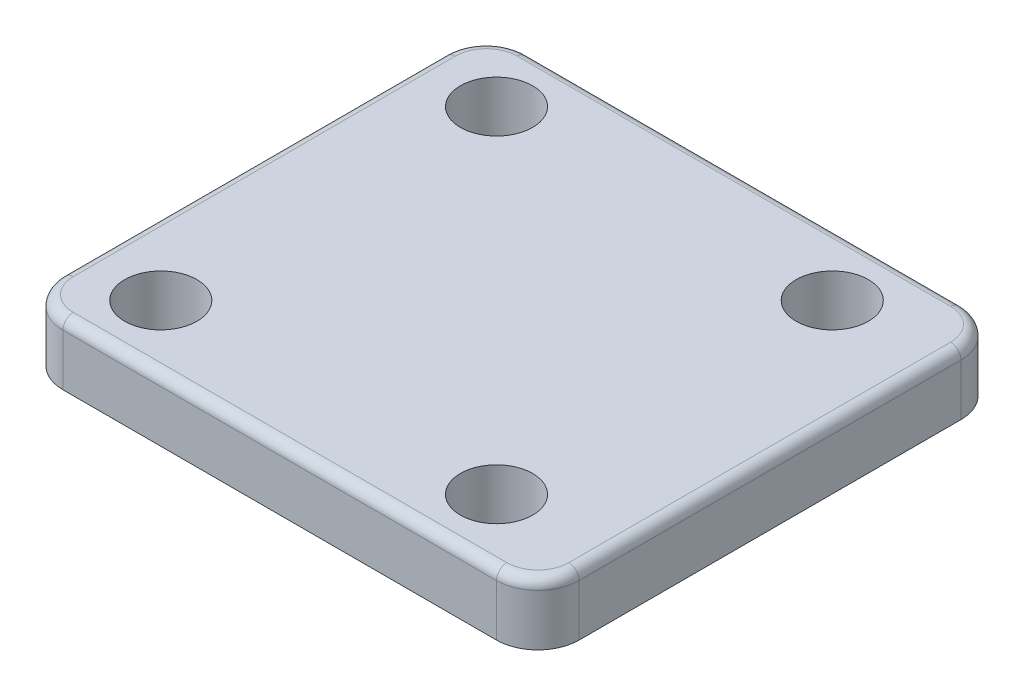
SolidWorks part; units mm, degrees
material "6061 Alloy"
ref_plane "Front Plane" through (0, 0, 0) normal (0, 0, 1) x (1, 0, 0)
ref_plane "Top Plane" through (0, 0, 0) normal (0, 1, 0) x (1, 0, 0)
ref_plane "Right Plane" through (0, 0, 0) normal (1, 0, 0) x (0, 0, -1)
sketch "Sketch1" plane through (0, 0, 0) normal (0, 1, 0) x (1, 0, 0)
  line L1 (-21, -22.5) -> (21, -22.5)
  line L2 (-25, -18.5) -> (-25, 18.5)
  line L3 (-21, 22.5) -> (21, 22.5)
  line L4 (25, -18.5) -> (25, 18.5)
  line L5 (-25, -22.5) -> (25, 22.5) construction
  line L6 (-25, 22.5) -> (25, -22.5) construction
  arc A0 (25, -18.5) -> (21, -22.5) centre (21, -18.5) cw
  arc A1 (-21, -22.5) -> (-25, -18.5) centre (-21, -18.5) cw
  arc A2 (25, 18.5) -> (21, 22.5) centre (21, 18.5) ccw
  arc A3 (-25, 18.5) -> (-21, 22.5) centre (-21, 18.5) cw
  point P0 (0, 0)
  dimension "D3" = 4
  dimension "D1" = 45
  dimension "D2" = 50
extrude "Boss-Extrude1" add sketch "Sketch1" along normal blind 6
fillet "Fillet1" radius 1 8 edges at (0, 6, 22.5) (-23.8284, 6, 21.3284) (-25, 6, 0) (-23.8284, 6, -21.3284) (0, 6, -22.5) (23.8284, 6, -21.3284) (25, 6, 0) (23.8284, 6, 21.3284)
sketch "Sketch2" plane through (0, 0, 0) normal (0, -1, 0) x (1, 0, 0)
  line L1 (-25, -18.5) -> (-25, 18.5) construction
  circle A0 centre (-1.5, 0) radius 16
  dimension "D1" = 32
  dimension "D2" = 23.5
  dimension "D3" = 1.5
extrude "Boss-Extrude2" add sketch "Sketch2" along normal blind 0.5
sketch "Sketch3" plane through (0, -0.5, 0) normal (0, -1, 0) x (-1, 0, 0)
  circle A0 centre (1.5, 0) radius 15
  circle A1 centre (1.5, 0) radius 16 construction
  dimension "D1" = 1
extrude "Boss-Extrude3" add sketch "Sketch3" along normal blind 0.5
fillet "Fillet2" radius 1 1 edges at (-1.5, -0.5, -15) profile chamfer first distance on face at (-1.5, -0.5, -15)
sketch "Sketch5" plane through (0, 0, 0) normal (0, -1, 0) x (-1, 0, 0)
  line L0 (11.5, 10) -> (1.5, 0) construction
  line L1 (-14.7635, -16.2635) -> (-8.5, -10) construction
  line L2 (1.5, 4.7757) -> (1.5, -8.8901) construction
  line L3 (-4.085, 0) -> (8.1701, 0) construction
  circle A0 centre (1.5, 0) radius 23 construction
  circle A2 centre (17.7635, 16.2635) radius 3.5
  circle A3 centre (1.5, 0) radius 15.5 construction
  dimension "D1" = 46
  dimension "D2" = 7
  dimension "D4" = 8.8901
  dimension "D5" = 4.7757
  dimension "D6" = 6.6701
  dimension "D7" = 5.585
  dimension "D8" = 45
  dimension "D11" = 10
  dimension "D13" = 10
extrude "Cut-Extrude2" cut sketch "Sketch5" against normal blind 10 contours A2
pattern_circular "CirPattern2" count 4 over 360 about axis through (-1.5, 0, 0) along (0, -1, 0) of "Cut-Extrude2"
